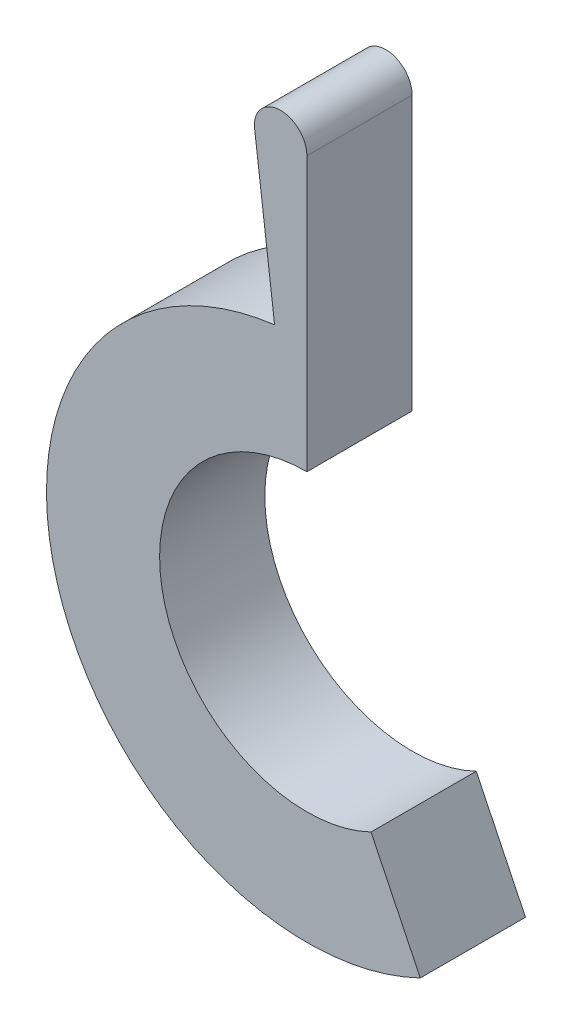
SolidWorks part; units mm, degrees
ref_plane "Plano frontal" through (0, 0, 0) normal (0, 0, 1) x (1, 0, 0)
ref_plane "Plano superior" through (0, 0, 0) normal (0, 1, 0) x (1, 0, 0)
ref_plane "Plano direito" through (0, 0, 0) normal (1, 0, 0) x (0, 0, -1)
sketch "Esboço1" plane through (0, 0, 0) normal (0, 0, 1) x (1, 0, 0)
  line L0 (0, 0) -> (10, 0) construction
  line L1 (0, 0) -> (-10, 0) construction
  line L2 (-10, 0) -> (-10, -9.798) construction
  line L6 (0, 20) -> (0, 40)
  line L7 (-5, 40) -> (-3.0699, 24.5589)
  line L8 (6.0951, -12.6035) -> (10.7753, -22.2813)
  line L9 (0, 20) -> (0, 14)
  arc A2 (0, 24.75) -> (-3.0699, 24.5589) centre (0, 0) ccw construction
  arc A3 (0, 40) -> (-4.9231, 39.3846) centre (-2.5, 40) ccw
  arc A4 (-3.0699, 24.5589) -> (10.7753, -22.2813) centre (0, 0) ccw
  arc A5 (0, 14) -> (6.0951, -12.6035) centre (0, 0) ccw
  dimension "D1" = 49.5
  dimension "D2" = 20
  dimension "D3" = 10
  dimension "D4" = 5
extrude "Ressalto-extrusão1" add sketch "Esboço1" along normal blind 10 contours A4 L6 A3 L7 region at (-0.7606, 17, 0)
